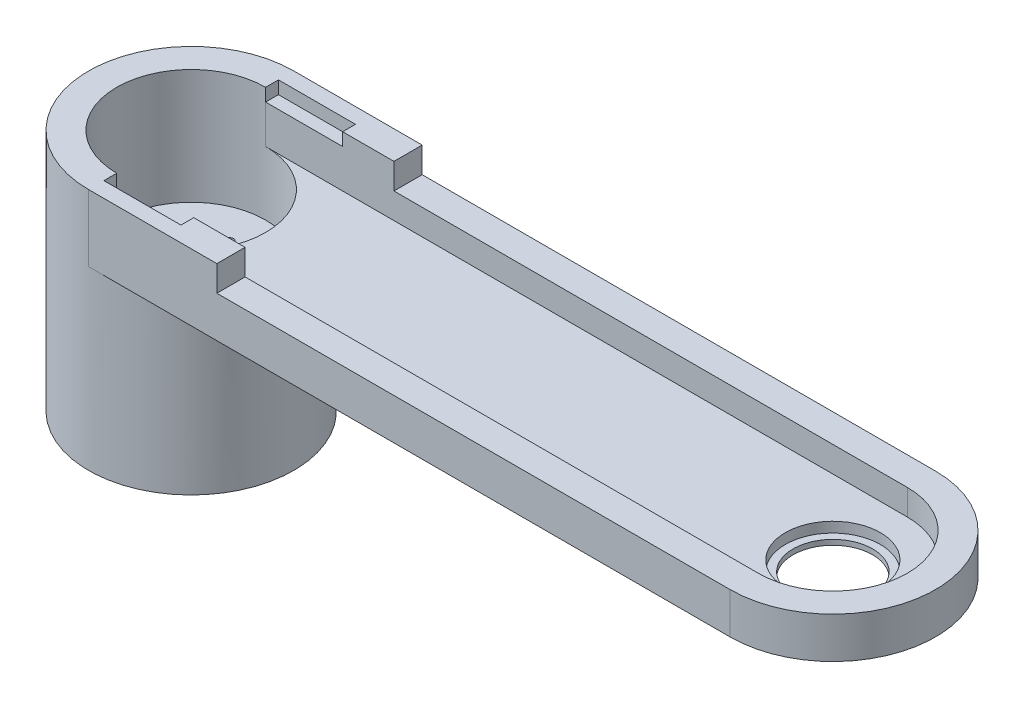
SolidWorks part; units mm, degrees
note: The reader was unsure of these and kept them because the rebuilt part matched: shared geometry of "Sketch7<2>".
ref_plane "Front Plane" through (0, 0, 0) normal (0, 0, 1) x (1, 0, 0)
ref_plane "Top Plane" through (0, 0, 0) normal (0, 1, 0) x (1, 0, 0)
ref_plane "Right Plane" through (0, 0, 0) normal (1, 0, 0) x (0, 0, -1)
sketch "Sketch1" plane through (0, 0, 0) normal (0, 1, 0) x (1, 0, 0)
  line L0 (0, 0) -> (250, 0) construction
  line L1 (0, 29) -> (250, 29)
  line L2 (0, -40) -> (250, -40)
  line L3 (0, -29) -> (250, -29)
  line L4 (0, 40) -> (250, 40)
  arc A0 (0, 29) -> (0, -29) centre (0, 0) ccw
  arc A1 (250, -29) -> (250, 29) centre (250, 0) ccw
  arc A2 (0, 40) -> (0, -40) centre (0, 0) ccw
  arc A3 (250, -40) -> (250, 40) centre (250, 0) ccw
  dimension "D1" = 58
  dimension "D3" = 40
  dimension "D2" = 250
extrude "Boss-Extrude1" add sketch "Sketch1" along normal blind 20
sketch "Sketch2" plane through (0, 0, 0) normal (0, -1, 0) x (1, 0, 0)
  circle A0 centre (0, 0) radius 29
  circle A1 centre (0, 0) radius 40
  arc A3 (0, 29) -> (0, -29) centre (0, 0) ccw construction
  arc A4 (0, 40) -> (0, -40) centre (0, 0) ccw construction
extrude "Boss-Extrude2" add sketch "Sketch2" along normal blind 24.8
sketch "Sketch3" plane through (0, -24.8, 0) normal (0, -1, 0) x (1, 0, 0)
  circle A0 centre (0, 0) radius 40 construction
  circle A1 centre (0, 0) radius 40
extrude "Boss-Extrude3" add sketch "Sketch3" along normal blind 5
sketch "Sketch4" plane through (0, 0, 0) normal (0, -1, 0) x (1, 0, 0)
  line L0 (250, -40) -> (0, -40) construction
  line L1 (0, 40) -> (250, 40) construction
  line L2 (250, -40) -> (0, -40)
  line L3 (0, 40) -> (250, 40)
  arc A0 (250, -40) -> (250, 40) centre (250, 0) ccw construction
  arc A1 (250, -40) -> (250, 40) centre (250, 0) ccw
  arc A2 (0, -40) -> (27.55, -29) centre (0, 0) ccw construction
  arc A3 (27.55, -29) -> (27.55, 29) centre (0, 0) ccw construction
  arc A4 (27.55, 29) -> (0, 40) centre (0, 0) ccw construction
  arc A5 (0, -40) -> (27.55, -29) centre (0, 0) ccw
  arc A6 (27.55, -29) -> (27.55, 29) centre (0, 0) ccw
  arc A7 (27.55, 29) -> (0, 40) centre (0, 0) ccw
extrude "Boss-Extrude4" add sketch "Sketch4" along normal blind 6
sketch "Sketch5" plane through (0, -24.8, 0) normal (0, 1, 0) x (1, 0, 0)
  circle A0 centre (0, 0) radius 15 construction
  circle A1 centre (0, 15) radius 1.5
  circle A2 centre (15, 0) radius 1.5
  circle A3 centre (0, -15) radius 1.5
  circle A4 centre (-15, 0) radius 1.5
  point P14 (0, 0)
  dimension "D1" = 30
  dimension "D2" = 3
  dimension "D3" = 4
extrude "Cut-Extrude1" cut sketch "Sketch5" against normal through all both and the other way through all
sketch "Sketch6" plane through (0, 0, 0) normal (0, 0, 1) x (1, 0, 0)
  line L1 (0, 20) -> (30, 20)
  line L2 (0, 20) -> (0, 15)
  line L3 (0, 15) -> (30, 15)
  line L4 (30, 20) -> (30, 15)
  dimension "D1" = 5
  dimension "D2" = 30
extrude "Cut-Extrude2" cut sketch "Sketch6" against normal offset from surface 5 and the other way offset from surface (34 mm away) 5 up to face at (125, 10, -29) offset beyond the face yes other way up to face at (125, 10, 29)
sketch "Sketch7" plane through (0, 0, 0) normal (0, 1, 0) x (1, 0, 0)
  circle A0 centre (250, 0) radius 15.5
  arc A2 (250, -29) -> (250, 29) centre (250, 0) ccw construction
  circle A3 centre (250, 0) radius 18.5
  dimension "D1" = 31
  dimension "D2" = 37
extrude "Cut-Extrude3" cut sketch "Sketch7" against normal blind 4
extrude "Cut-Extrude4" cut sketch "Sketch7<2>" against normal through all both and the other way through all contours A0
sketch "Sketch7<2>" plane through (0, 0, 0) normal (0, 1, 0) x (1, 0, 0) same geometry as "Sketch7"
sketch "Sketch9" plane through (0, 20, 0) normal (0, 1, 0) x (1, 0, 0)
  line L0 (0, -40) -> (250, -40) construction
  line L1 (250, 40) -> (0, 40) construction
  line L2 (50, -40) -> (250, -40)
  line L3 (250, 40) -> (50, 40)
  line L4 (0, 0) -> (250, 0) construction
  line L5 (50, 40) -> (50, -40)
  arc A0 (250, -40) -> (250, 40) centre (250, 0) ccw construction
  arc A1 (250, -40) -> (250, 40) centre (250, 0) ccw
  dimension "D1" = 200
extrude "Cut-Extrude5" cut sketch "Sketch9" against normal blind 10
sketch "Sketch10" plane through (0, -29.8, 0) normal (0, -1, 0) x (1, 0, 0)
  circle A0 centre (-15, 0) radius 1.5 construction
  circle A1 centre (0, 0) radius 40
  circle A2 centre (0, 0) radius 40
  circle A3 centre (0, -15) radius 1.5 construction
  circle A4 centre (15, 0) radius 1.5 construction
  circle A5 centre (0, 15) radius 1.5 construction
  circle A6 centre (-15, 0) radius 1.5
  circle A7 centre (0, -15) radius 1.5
  circle A8 centre (15, 0) radius 1.5
  circle A9 centre (0, 15) radius 1.5
  dimension "D1" = 0
extrude "Boss-Extrude5" add sketch "Sketch10" along normal blind 45
sketch "Sketch11" plane through (0, -74.8, 0) normal (0, -1, 0) x (1, 0, 0)
  circle A0 centre (0, 0) radius 8.5
  dimension "D1" = 17
extrude "Cut-Extrude6" cut sketch "Sketch11" against normal blind 6
